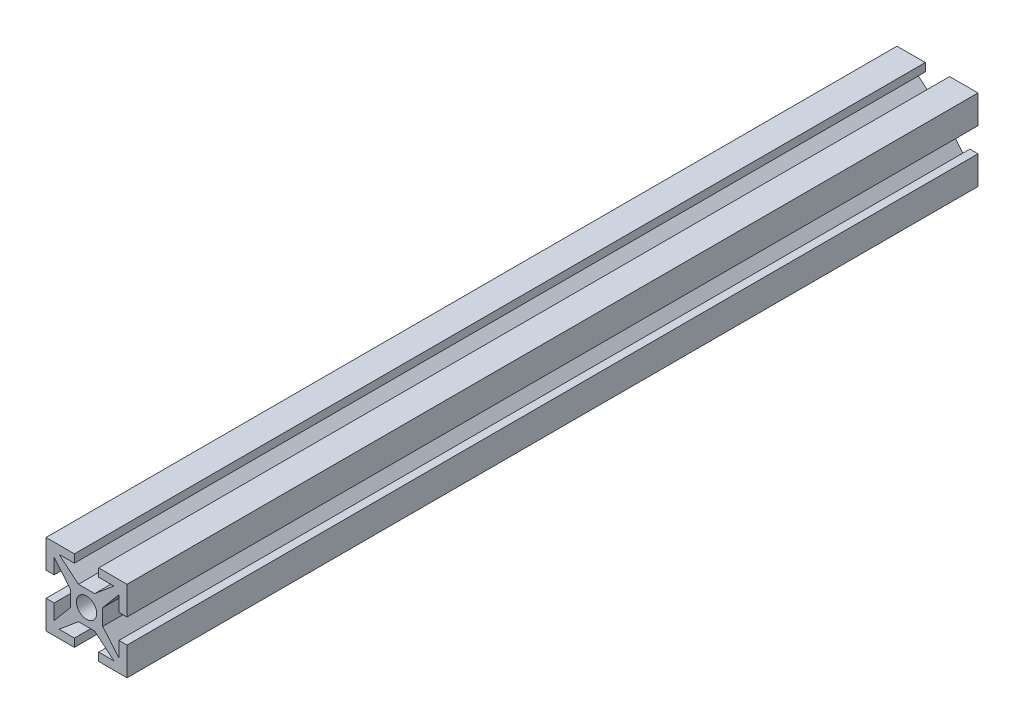
SolidWorks part; units mm, degrees
ref_plane "Front Plane" through (0, 0, 0) normal (0, 0, 1) x (1, 0, 0)
ref_plane "Top Plane" through (0, 0, 0) normal (0, 1, 0) x (1, 0, 0)
ref_plane "Right Plane" through (0, 0, 0) normal (1, 0, 0) x (0, 0, -1)
sketch "Esquisse2" plane through (0, 0, 0) normal (0, 0, 1) x (1, 0, 0)
  line L0 (-1, -2) -> (1, -2)
  line L1 (1, -2) -> (3.3835, -4)
  line L2 (3.3835, -4) -> (1.5, -4)
  line L3 (1.5, -4) -> (1.5, -5)
  line L4 (1.5, -5) -> (5, -5)
  line L5 (-1, -2) -> (-3.3835, -4)
  line L6 (-3.3835, -4) -> (-1.5, -4)
  line L7 (-1.5, -4) -> (-1.5, -5)
  line L8 (-1.5, -5) -> (-5, -5)
  line L9 (-5, -5) -> (-5, -1.5)
  line L10 (-5, -1.5) -> (-4, -1.5)
  line L11 (-4, -1.5) -> (-4, -3.3835)
  line L12 (-4, -3.3835) -> (-2, -1)
  line L13 (-2, -1) -> (-2, 1)
  line L14 (-2, 1) -> (-4, 3.3835)
  line L15 (-4, 3.3835) -> (-4, 1.5)
  line L16 (-4, 1.5) -> (-5, 1.5)
  line L17 (-5, 1.5) -> (-5, 5)
  line L18 (-5, 5) -> (-1.5, 5)
  line L19 (-1.5, 5) -> (-1.5, 4)
  line L20 (-1.5, 4) -> (-3.3835, 4)
  line L21 (-3.3835, 4) -> (-1, 2)
  line L22 (-1, 2) -> (1, 2)
  line L23 (1, 2) -> (3.3835, 4)
  line L24 (3.3835, 4) -> (1.5, 4)
  line L25 (1.5, 4) -> (1.5, 5)
  line L26 (1.5, 5) -> (5, 5)
  line L27 (5, 5) -> (5, 1.5)
  line L28 (5, 1.5) -> (4, 1.5)
  line L29 (4, 1.5) -> (4, 3.3835)
  line L30 (4, 3.3835) -> (2, 1)
  line L31 (2, -1) -> (2, 1)
  line L32 (2, -1) -> (4, -3.3835)
  line L33 (4, -3.3835) -> (4, -1.5)
  line L34 (4, -1.5) -> (5, -1.5)
  line L35 (5, -1.5) -> (5, -5)
  circle A0 centre (0, 0) radius 1.25
  point P4 (0, -2)
  point P34 (0, 2)
  point P40 (2, 0)
  dimension "D4" = 2.5
  dimension "D1" = 2
  dimension "D2" = 3.5
  dimension "D3" = 1
  dimension "D5" = 10
  dimension "D6" = 10
  dimension "D7" = 140
  dimension "D8" = 4
  dimension "D9" = 4
  dimension "D10" = 3.5
  dimension "D11" = 3
extrude "Boss.-Extru.1" add sketch "Esquisse2" along normal blind 105
